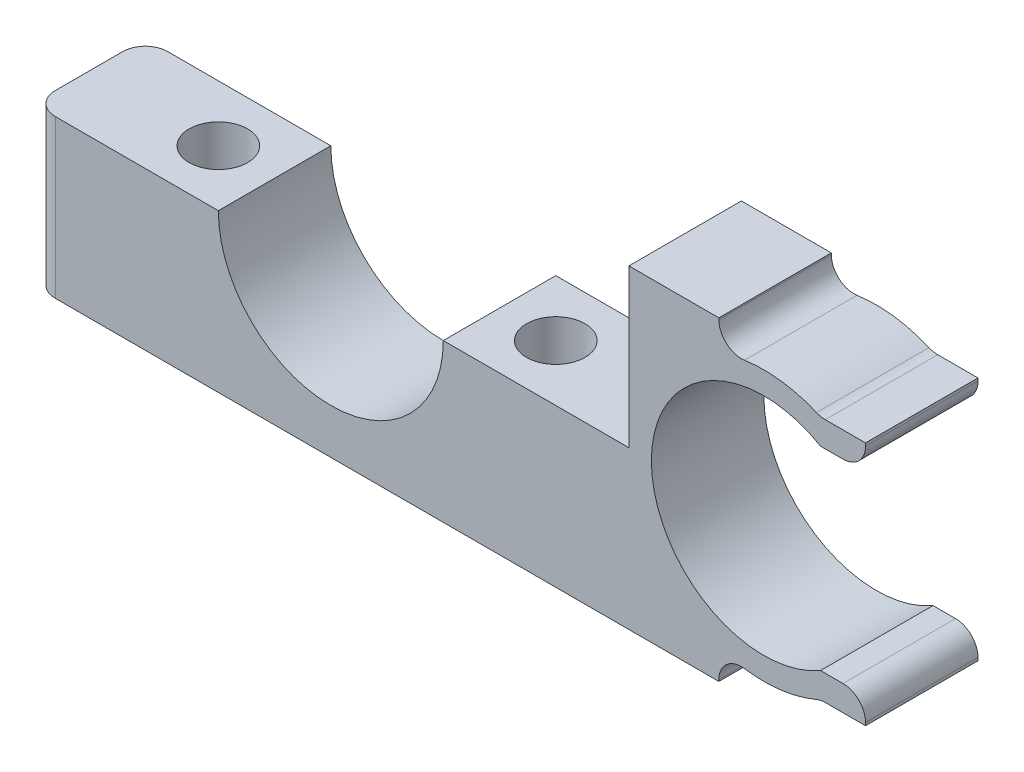
SolidWorks part; units mm, degrees
ref_plane "Front Plane" through (0, 0, 0) normal (0, 0, 1) x (1, 0, 0)
ref_plane "Top Plane" through (0, 0, 0) normal (0, 1, 0) x (1, 0, 0)
ref_plane "Right Plane" through (0, 0, 0) normal (1, 0, 0) x (0, 0, -1)
sketch "Sketch1" plane through (0, 0, 0) normal (0, 0, 1) x (1, 0, 0)
  line L0 (10, 0) -> (26.5, 0)
  line L1 (26.5, 0) -> (38.5, 0) construction
  line L2 (34.5, -11.3137) -> (34.5, -14)
  line L3 (26.5, 14) -> (34.5, 14)
  line L4 (26.5, 14) -> (26.5, 0)
  line L5 (-26.5, 0) -> (-10, 0)
  line L6 (-26.5, 0) -> (-26.5, -14)
  line L7 (-26.5, -14) -> (26.5, -14)
  line L8 (26.5, 0) -> (49, 0) construction
  line L9 (26.5, -14) -> (34.5, -14)
  line L10 (34.5, 14) -> (34.5, 11.3137)
  line L11 (43.5406, -10.89) -> (43.5406, 10.89) construction
  line L12 (0, 0) -> (38.5, 0) construction
  line L13 (43.5406, 10.89) -> (47.5406, 10.89)
  line L14 (43.5406, 10.89) -> (43.5406, 8.6367) construction
  line L15 (43.5406, 8.6367) -> (47.5406, 8.6367)
  line L16 (47.5406, 10.89) -> (47.5406, 8.6367)
  line L17 (43.5406, -8.6367) -> (47.5406, -8.6367)
  line L18 (43.5406, -8.6367) -> (43.5406, -10.89) construction
  line L19 (43.5406, -10.89) -> (47.5406, -10.89)
  line L20 (47.5406, -8.6367) -> (47.5406, -10.89)
  arc A0 (-10, 0) -> (10, 0) centre (0, 0) ccw
  arc A1 (43.5406, 8.6367) -> (43.5406, -8.6367) centre (38.5, 0) ccw
  arc A2 (34.5, -11.3137) -> (43.5406, -10.89) centre (38.5, 0) ccw
  arc A3 (43.5406, 10.89) -> (34.5, 11.3137) centre (38.5, 0) ccw
  dimension "D3" = 20
  dimension "D5" = 20
  dimension "D6" = 24
  dimension "D1" = 12
  dimension "D2" = 53
  dimension "D4" = 14
  dimension "D7" = 28
  dimension "D8" = 8
  dimension "D9" = 4
  dimension "D10" = 38.5
extrude "Boss-Extrude1" add sketch "Sketch1" along normal blind 10
fillet "Fillet1" radius 2 8 edges at (47.5406, -8.6367, 5) (47.5406, 8.6367, 5) (-26.5, -7, 0) (-26.5, -7, 10) (43.5406, 10.89, 5) (43.5406, -10.89, 5) (34.5, -11.3137, 5) (34.5, 11.3137, 5)
sketch "Sketch4" plane through (0, 0, 0) normal (0, 1, 0) x (1, 0, 0)
  line L0 (-15, -5) -> (15, -5) construction
  line L1 (0, 0) -> (0, -5) construction
  circle A0 centre (-15, -5) radius 2.6
  circle A1 centre (15, -5) radius 2.6
  point P7 (0, -5)
  dimension "D2" = 5.2
  dimension "D1" = 30
  dimension "D3" = 5
extrude "Cut-Extrude2" cut sketch "Sketch4" against normal through all
